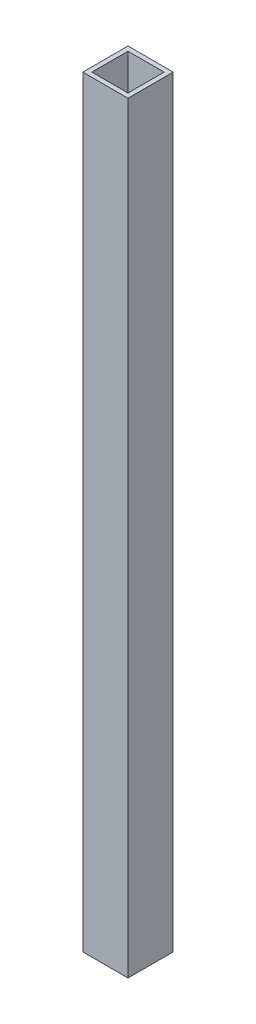
SolidWorks part; units mm, degrees
ref_plane "Plano frontal" through (0, 0, 0) normal (0, 0, 1) x (1, 0, 0)
ref_plane "Plano superior" through (0, 0, 0) normal (0, 1, 0) x (1, 0, 0)
ref_plane "Plano direito" through (0, 0, 0) normal (1, 0, 0) x (0, 0, -1)
sketch "Esboço1" plane through (0, 0, 0) normal (0, 1, 0) x (1, 0, 0)
  line L1 (0, 0) -> (20, 0)
  line L2 (0, 0) -> (0, 20)
  line L3 (0, 20) -> (20, 20)
  line L4 (20, 0) -> (20, 20)
  dimension "D1" = 20
extrude "Extrusão-Fina1" add sketch "Esboço1" along normal blind 337 thin thin type one direction reverse wall 2
